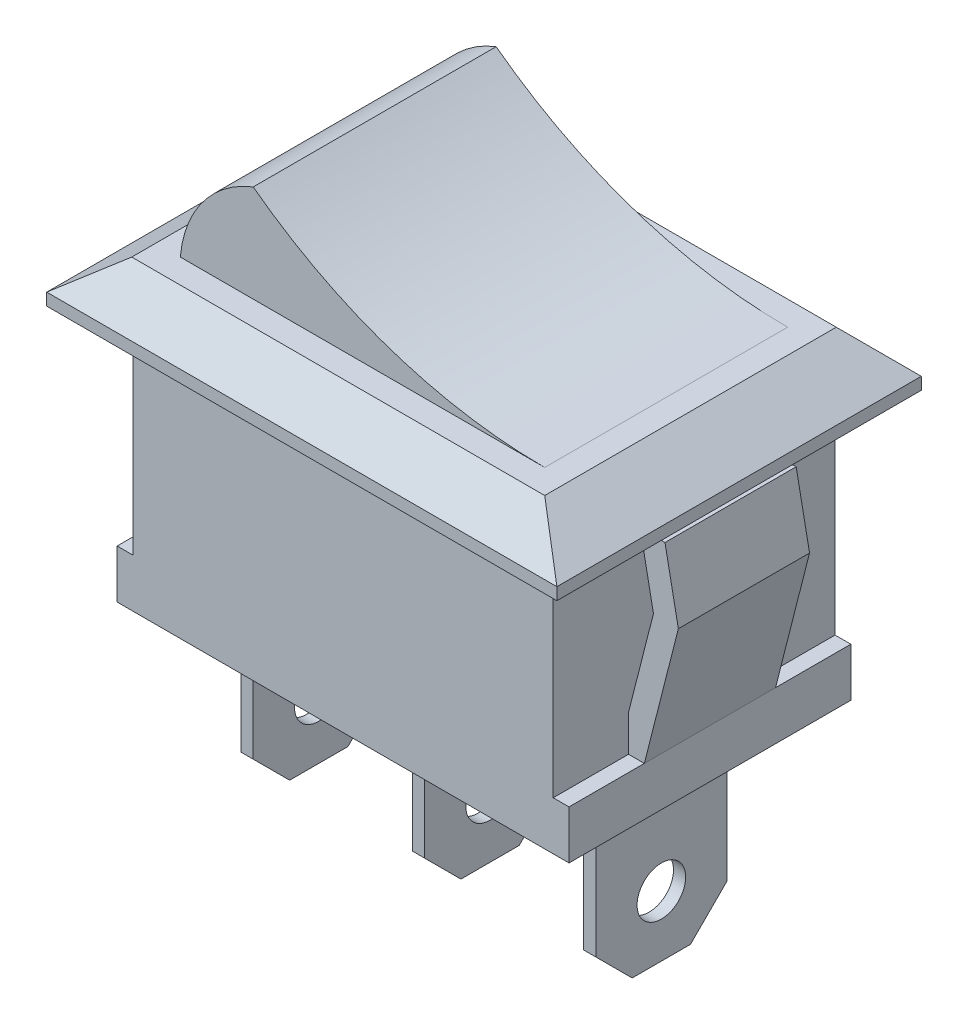
SolidWorks part; units mm, degrees
material "PEI"
ref_plane "前视基准面" through (0, 0, 0) normal (0, 0, 1) x (1, 0, 0)
ref_plane "上视基准面" through (0, 0, 0) normal (0, 1, 0) x (1, 0, 0)
ref_plane "右视基准面" through (0, 0, 0) normal (1, 0, 0) x (0, 0, -1)
other "Configuration Table"
sketch "草图1" plane through (0, 0, 0) normal (0, 0, 1) x (1, 0, 0)
  line L0 (-7.838, 0) -> (11.651, 0) construction
  line L1 (0, 17.1588) -> (0, -8.7559) construction
  line L3 (-8.65, 10.8) -> (8.65, 10.8)
  line L4 (-8.65, 10.8) -> (-8.65, 0)
  line L5 (-8.65, 0) -> (8.65, 0)
  line L6 (8.65, 10.8) -> (8.65, 0)
  dimension "D1" = 17.3
  dimension "D2" = 10.8
extrude "凸台-拉伸1" add sketch "草图1" along normal blind 5.8 and the other way blind 5.8
sketch "草图2" plane through (0, 0, 0) normal (0, 0, 1) x (1, 0, 0)
  line L0 (-10.5, 11.3) -> (-8.5, 12.8)
  line L1 (-10.5, 12.8) -> (8.5, 12.8)
  line L2 (-10.5, 12.8) -> (-10.5, 10.8)
  line L3 (-10.5, 10.8) -> (10.5, 10.8)
  line L4 (10.5, 11.3) -> (10.5, 10.8)
  line L5 (-8.5, 12.8) -> (8.5, 12.8)
  line L6 (8.5, 12.8) -> (10.5, 11.3)
  point P4 (0, 10.8)
  point P8 (0, 0)
  dimension "D1" = 2
  dimension "D2" = 21
  dimension "D3" = 2
  dimension "D4" = 0.5
  dimension "D5" = 0.5
  dimension "D6" = 2
extrude "凸台-拉伸2" add sketch "草图2" along normal blind 7.5 and the other way blind 7.5 contours L6 L1 L0 L2 L3 L4 region at (0, 11.7615, 0)
chamfer "倒角1" distance 1.5 angle 45 2 edges at (0, 12.8, -7.5) (0, 12.8, 7.5)
sketch "草图3" plane through (0, 0, 0) normal (0, 0, 1) x (1, 0, 0)
  line L0 (-8.5, 12.8) -> (8.5, 12.8) construction
  line L1 (-8.5, 12.8) -> (8.5, 12.8)
  line L2 (-10.5, 11.3) -> (-10.5, 10.8) construction
  arc A1 (-4.5, 16.8) -> (7.5, 12.8) centre (7.5, 32.8) ccw
  arc A2 (-7.5, 12.8) -> (-4.5, 16.8) centre (-2.801, 12.4007) cw
  point P12 (0, 12.8)
  dimension "D1" = 15
  dimension "D2" = 7.5
  dimension "D3" = 4
  dimension "D4" = 6
extrude "凸台-拉伸3" add sketch "草图3" along normal blind 5 and the other way blind 5 contours A2 L1 A1 region at (-3.0366, 14.118, 0)
sketch "草图4" plane through (0, 0, 0) normal (0, 0, 1) x (1, 0, 0)
  line L0 (-8.65, 0) -> (8.65, 0) construction
  line L1 (-9.3, 0) -> (9.3, 0)
  line L2 (-9.3, 0) -> (-9.3, 2)
  line L3 (-9.3, 2) -> (9.3, 2)
  line L4 (9.3, 0) -> (9.3, 2)
  line L5 (0, 10.8) -> (0, 0) construction
  line L6 (8.65, 10.8) -> (-8.65, 10.8) construction
  dimension "D1" = 18.6
  dimension "D2" = 2
extrude "凸台-拉伸4" add sketch "草图4" along normal up to surface and the other way up to surface up to face at (0, 5.4, 5.8) other way up to face at (0, 5.4, -5.8)
sketch "草图5" plane through (0, 0, 0) normal (0, 0, 1) x (1, 0, 0)
  line L0 (-9.3, 2) -> (-10.7, 7.5)
  line L1 (-10.7, 7.5) -> (-10.15, 10.3)
  line L2 (0, 0) -> (0, 10.503) construction
  line L3 (-9.3, 0) -> (9.3, 0) construction
  line L4 (-10.5, 10.8) -> (10.5, 10.8) construction
  line L5 (-8.65, 10.8) -> (-8.65, 2) construction
  line L6 (-8.65, 3.5003) -> (-9.6753, 7.5283)
  line L7 (-9.6753, 7.5283) -> (-9.1688, 10.1073)
  line L8 (-10.15, 10.3) -> (-9.1309, 10.3)
  line L9 (-9.1309, 10.3) -> (-9.1688, 10.1073)
  line L10 (-9.3, 2) -> (-8.65, 2)
  line L11 (-8.65, 2) -> (-8.65, 3.5003)
  line L12 (-8.3309, 2.2467) -> (-9.6753, 7.5283) construction
  line L13 (8.65, 2) -> (8.65, 3.5003)
  line L14 (9.3, 2) -> (8.65, 2)
  line L15 (9.1309, 10.3) -> (9.1688, 10.1073)
  line L16 (10.15, 10.3) -> (9.1309, 10.3)
  line L17 (9.6753, 7.5283) -> (9.1688, 10.1073)
  line L18 (8.65, 3.5003) -> (9.6753, 7.5283)
  line L19 (10.7, 7.5) -> (10.15, 10.3)
  line L20 (9.3, 2) -> (10.7, 7.5)
  line L22 (-0.25, 0) -> (0.25, 0)
  line L23 (-0.25, 0) -> (-0.25, -7.4)
  line L24 (-0.25, -7.4) -> (0.25, -7.4)
  line L25 (0.25, 0) -> (0.25, -7.4)
  line L26 (-7.3, 0) -> (-6.8, 0)
  line L27 (-7.3, 0) -> (-7.3, -7.4)
  line L28 (-7.3, -7.4) -> (-6.8, -7.4)
  line L29 (-6.8, 0) -> (-6.8, -7.4)
  line L30 (6.8, 0) -> (7.3, 0)
  line L31 (6.8, 0) -> (6.8, -7.4)
  line L32 (6.8, -7.4) -> (7.3, -7.4)
  line L33 (7.3, 0) -> (7.3, -7.4)
  dimension "D1" = 10.7
  dimension "D2" = 7.5
  dimension "D3" = 0.5
  dimension "D4" = 1.5
  dimension "D6" = 0.5
  dimension "D7" = 14.6
  dimension "D8" = 7.4
  dimension "D5" = 1
extrude "凸台-拉伸5" add sketch "草图5" along normal blind 2.7 and the other way blind 2.7
sketch "草图6" plane through (-7.3, 0, 0) normal (-1, 0, 0) x (0, 0, 1)
  line L0 (-2.7, -7.4) -> (2.7, -7.4) construction
  line L1 (-2.7, -5.9) -> (-1.2, -7.4)
  line L2 (-2.7, 0) -> (-2.7, -7.4) construction
  line L3 (-1.2, -7.4) -> (1.2, -7.4)
  line L4 (1.2, -7.4) -> (2.7, -5.9)
  line L5 (2.7, 0) -> (2.7, -7.4) construction
  line L6 (2.7, -5.9) -> (2.7, -7.4)
  circle A0 centre (0, -4.9) radius 1
  circle A1 centre (0, -0.9) radius 0.75
  line M2 (-2.7, -7.4) -> (2.7, -7.4)
  line M3 (2.7, -7.4) -> (2.7, 0)
  line M5 (-2.7, 0) -> (-2.7, -7.4)
  dimension "D1" = 2
  dimension "D2" = 1.5
  dimension "D3" = 2.5
  dimension "D4" = 4
  dimension "D5" = 1.5
  dimension "D6" = 1.5
  dimension "D7" = 1.5
extrude "切除-拉伸1" cut sketch "草图6" against normal through all contours A1 | L1 M5 M2 | L4 M2 M3 | A0 region at (-7.3, -6.9, 2.2) region at (-7.3, -6.9, -2.2) region at (-7.3, -4.9, 0) region at (-7.3, -0.9, 0)
